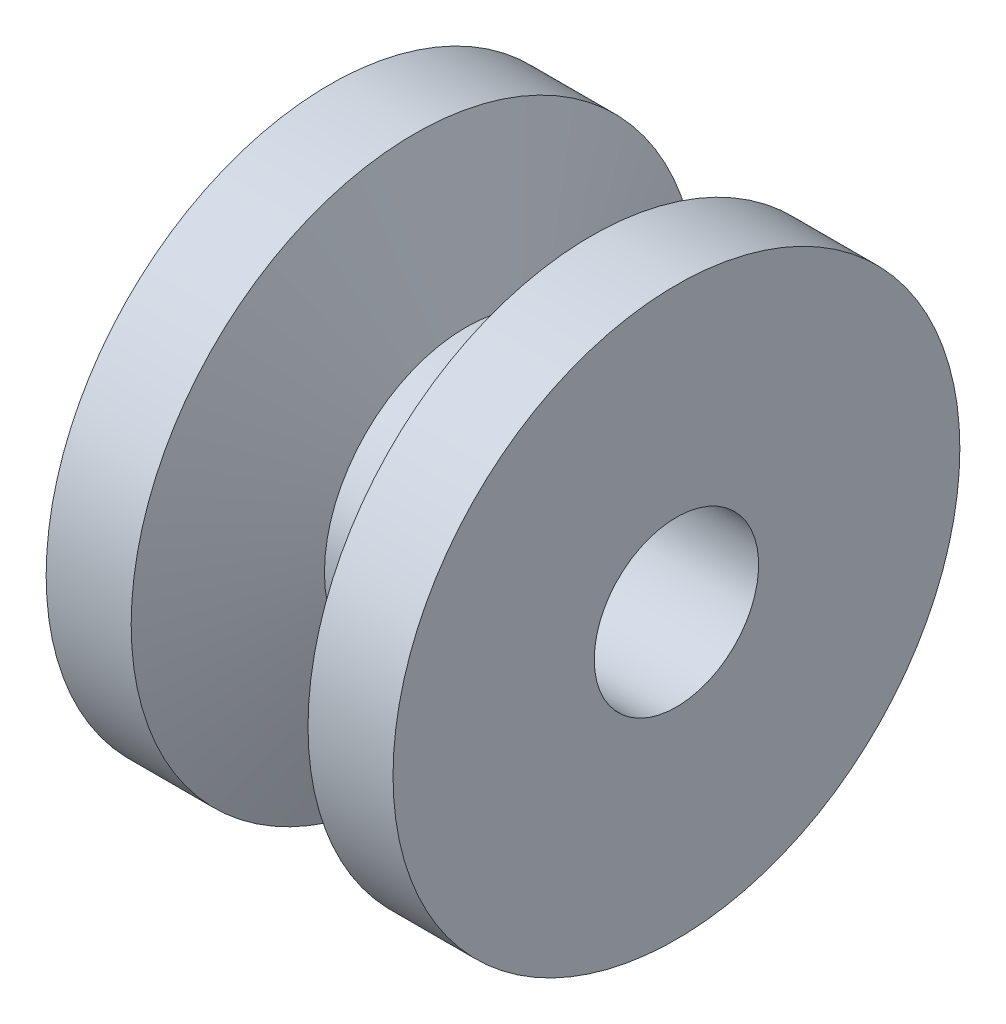
SolidWorks part; units mm, degrees
ref_plane "Front Plane" through (0, 0, 0) normal (0, 0, 1) x (1, 0, 0)
ref_plane "Top Plane" through (0, 0, 0) normal (0, 1, 0) x (1, 0, 0)
ref_plane "Right Plane" through (0, 0, 0) normal (1, 0, 0) x (0, 0, -1)
sketch "Sketch1" plane through (0, 0, 0) normal (0, 1, 0) x (1, 0, 0)
  line L1 (0, 12.7) -> (3.81, 12.7)
  line L2 (3.81, 12.7) -> (6.1212, 6.35)
  line L3 (6.1212, 6.35) -> (9.4232, 6.35)
  line L4 (9.4232, 6.35) -> (11.7344, 12.7)
  line L5 (11.7344, 12.7) -> (15.5444, 12.7)
  line L6 (15.5444, 12.7) -> (15.5444, 3.683)
  line L8 (0, 12.7) -> (0, 3.683)
  line L9 (0, 3.683) -> (15.5444, 3.683)
  dimension "D1" = 3.683
  dimension "D2" = 12.7
  dimension "D3" = 3.302
  dimension "D4" = 3.81
  dimension "D5" = 6.35
  dimension "D6" = 3.81
  dimension "D7" = 110
  dimension "D8" = 110
ref_axis "Axis1" through (0, 0, 0) along (1, 0, 0)
revolve "Revolve1" add sketch "Sketch1" angle 360 about axis through (0, 0, 0) along (1, 0, 0)
